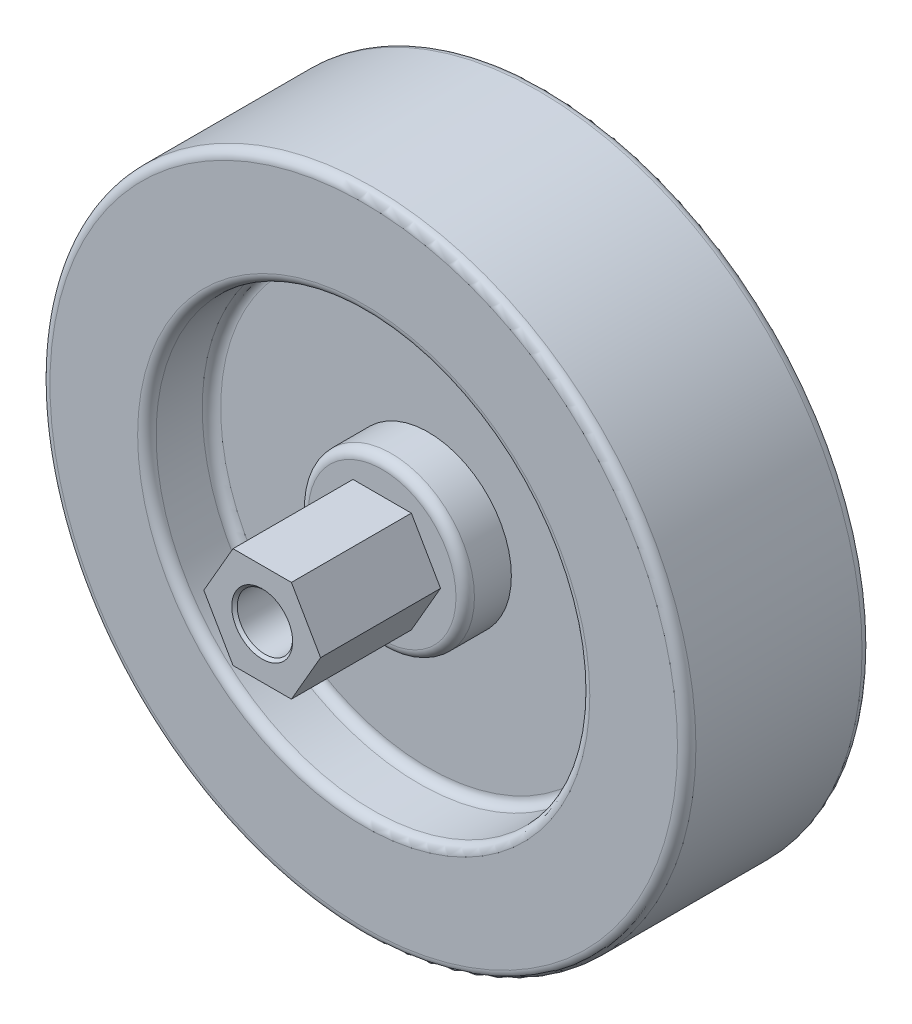
SolidWorks part; units mm, degrees
ref_plane "前视基准面" through (0, 0, 0) normal (0, 0, 1) x (1, 0, 0)
ref_plane "上视基准面" through (0, 0, 0) normal (0, 1, 0) x (1, 0, 0)
ref_plane "右视基准面" through (0, 0, 0) normal (1, 0, 0) x (0, 0, -1)
other "Configuration Table"
sketch "草图1" plane through (0, 0, 0) normal (0, 0, 1) x (1, 0, 0)
  circle A0 centre (0, 0) radius 35
  circle A1 centre (0, 0) radius 23.5
  dimension "D1" = 70
  dimension "D2" = 47
extrude "凸台-拉伸1" add sketch "草图1" along normal blind 20
sketch "草图2" plane through (0, 0, 0) normal (0, 0, 1) x (1, 0, 0)
  circle A0 centre (0, 0) radius 23.5
extrude "凸台-拉伸2" add sketch "草图2" along normal blind 18
sketch "草图3" plane through (0, 0, 18) normal (0, 0, 1) x (1, 0, 0)
  line L1 (6.3272, 0) -> (3.1636, 5.4795)
  line L2 (3.1636, 5.4795) -> (-3.1636, 5.4795)
  line L3 (-3.1636, 5.4795) -> (-6.3272, 0)
  line L4 (-6.3272, 0) -> (-3.1636, -5.4795)
  line L5 (-3.1636, -5.4795) -> (3.1636, -5.4795)
  line L6 (3.1636, -5.4795) -> (6.3272, 0)
  circle A1 centre (0, 0) radius 6.3272 construction
  dimension "D1" = 5.4795
  dimension "D2" = 12.6543
extrude "凸台-拉伸3" add sketch "草图3" along normal blind 13
sketch "草图4" plane through (0, 0, 18) normal (0, 0, 1) x (1, 0, 0)
  circle A0 centre (0, 0) radius 9
  circle A1 centre (0, 0) radius 23.5
  dimension "D1" = 18
  dimension "D2" = 47
extrude "切除-拉伸1" cut sketch "草图4" against normal blind 5
sketch "草图5" plane through (0, 0, 31) normal (0, 0, 1) x (1, 0, 0)
  circle A0 centre (0, 0) radius 3
  dimension "D1" = 6
extrude "切除-拉伸2" cut sketch "草图5" against normal blind 12
sketch "草图7" plane through (0, 0, 0) normal (0, 0, -1) x (-1, 0, 0)
  circle A0 centre (0, 0) radius 24
  dimension "D1" = 48
extrude "切除-拉伸3" cut sketch "草图7" against normal blind 2
fillet "圆角1" radius 1 7 edges at (9, 0, 18) (23.5, 0, 13) (23.5, 0, 20) (-24, 0, 2) (-24, 0, 0) (35, 0, 0) (35, 0, 20)
chamfer "倒角1" distance 0.3 angle 45 1 edges at (3, 0, 31)
sketch "草图8" plane through (0, 0, 2) normal (0, 0, -1) x (-1, 0, 0)
  point P0 (0, 0)
